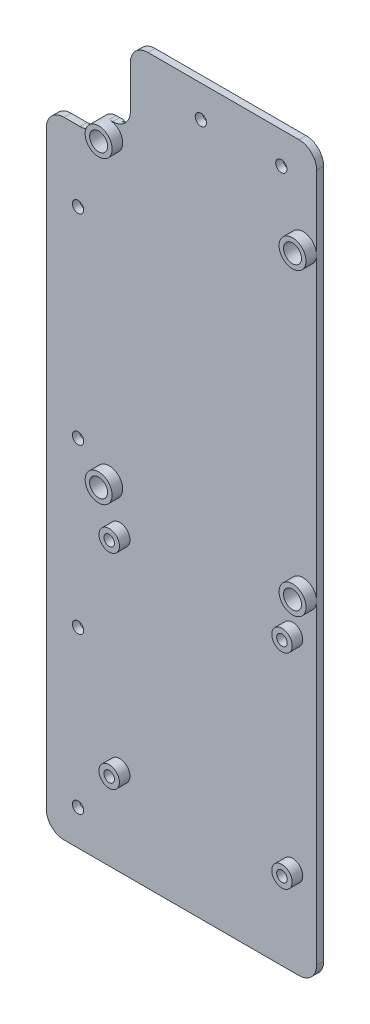
SolidWorks part; units mm, degrees
material "6063-T5"
ref_plane "Front Plane" through (0, 0, 0) normal (1, 0, 0) x (0, 1, 0)
ref_plane "Top Plane" through (0, 0, 0) normal (0, 0, 1) x (0, 1, 0)
ref_plane "Right Plane" through (0, 0, 0) normal (0, 1, 0) x (-1, 0, 0)
sketch "Sketch1" plane through (0, 0, 0) normal (0, 0, 1) x (0, 1, 0)
  line L1 (-42.5, -27.5) -> (42.5, -27.5) construction
  line L2 (-42.5, -27.5) -> (-42.5, 27.5) construction
  line L3 (-42.5, 27.5) -> (42.5, 27.5) construction
  line L4 (42.5, -27.5) -> (42.5, 27.5) construction
  line L5 (-42.5, -27.5) -> (42.5, 27.5) construction
  line L6 (-42.5, 27.5) -> (42.5, -27.5) construction
  circle A0 centre (-42.5, 27.5) radius 2.525
  circle A1 centre (42.5, 27.5) radius 2.525
  circle A2 centre (42.5, -27.5) radius 2.525
  circle A3 centre (-42.5, -27.5) radius 2.525
  circle A4 centre (42.5, 27.5) radius 3.825
  circle A5 centre (-42.5, 27.5) radius 3.825
  circle A6 centre (-42.5, -27.5) radius 3.825
  circle A7 centre (42.5, -27.5) radius 3.825
  point P0 (0, 0)
  dimension "D1" = 1.3
  dimension "D2" = 5.05
  dimension "D3" = 85
  dimension "D4" = 55
extrude "Boss-Extrude1" add sketch "Sketch1" along normal blind 3
sketch "Sketch3" plane through (0, 0, 0) normal (0, 0, -1) x (1, 0, 0)
  line L0 (-31.325, -42.5) -> (-31.325, 42.5)
  line L1 (-27.5, 46.325) -> (27.5, 46.325)
  line L2 (31.325, 42.5) -> (31.325, -42.5)
  line L3 (27.5, -46.325) -> (-27.5, -46.325)
  line L4 (27.5, 46.325) -> (27.5, 42.5) construction
  line L5 (27.5, 42.5) -> (31.325, 42.5) construction
  line L6 (-31.325, -42.5) -> (-27.5, -42.5) construction
  line L7 (-27.5, -42.5) -> (-27.5, -46.325) construction
  arc A0 (-31.325, 42.5) -> (-27.5, 46.325) centre (-27.5, 42.5) cw
  circle A1 centre (-27.5, 42.5) radius 3.825 construction
  arc A2 (31.325, 42.5) -> (27.5, 46.325) centre (27.5, 42.5) ccw
  circle A3 centre (27.5, 42.5) radius 3.825 construction
  arc A4 (-31.325, -42.5) -> (-27.5, -46.325) centre (-27.5, -42.5) ccw
  circle A5 centre (-27.5, -42.5) radius 3.825 construction
  arc A6 (27.5, -46.325) -> (31.325, -42.5) centre (27.5, -42.5) ccw
  circle A7 centre (27.5, -42.5) radius 3.825 construction
extrude "Boss-Extrude2" add sketch "Sketch3" along normal blind 2
sketch "Sketch4" plane through (0, 0, 0) normal (0, 0, 1) x (1, 0, 0)
  line L0 (-27.5, -46.325) -> (-45.325, -46.325)
  line L1 (-45.325, -46.325) -> (-45.325, 40.5)
  line L2 (-45.325, 40.5) -> (-31.325, 40.5)
  line L3 (-31.325, -42.5) -> (-31.325, 42.5) construction
  line L4 (-31.325, 40.5) -> (-31.325, -42.5)
  line L5 (-31.325, -42.5) -> (-27.5, -46.325)
  line L6 (31.325, 42.5) -> (31.325, 68.325)
  line L7 (31.325, 68.325) -> (-21.5, 68.325)
  line L8 (-21.5, 68.325) -> (-21.5, 46.325)
  line L9 (-27.5, 46.325) -> (27.5, 46.325) construction
  line L10 (-21.5, 46.325) -> (27.5, 46.325)
  line L11 (27.5, 46.325) -> (31.325, 42.5)
  line L12 (-36.325, -46.325) -> (-36.325, 40.5) construction
  line L13 (-21.5, 59.325) -> (31.325, 59.325) construction
  line L14 (-36.325, 40.5) -> (-36.325, 59.325) construction
  line L15 (-36.325, 59.325) -> (-21.5, 59.325) construction
  circle A0 centre (-27.5, 42.5) radius 2.525 construction
  circle A1 centre (-27.5, 42.5) radius 2.525 construction
  circle A2 centre (21.325, 59.325) radius 1.6
  circle A3 centre (-1.5, 59.325) radius 1.6
  circle A4 centre (-36.325, 20.5) radius 1.6
  circle A5 centre (-36.325, -36.325) radius 1.6
  dimension "D3" = 6
  dimension "D5" = 3.2
  dimension "D2" = 9
  dimension "D4" = 2
  dimension "D6" = 9
  dimension "D7" = 5
  dimension "D8" = 86.825
  dimension "D9" = 20
  dimension "D10" = 10
  dimension "D11" = 20
  dimension "D12" = 10
  dimension "D13" = 13
extrude "Boss-Extrude3" add sketch "Sketch4" against normal up to surface (2 mm away) up to face at (0, 0, -2)
sketch "Sketch6" plane through (0, 0, 3) normal (0, 0, 1) x (1, 0, 0)
  circle A0 centre (-27.5, 42.5) radius 2.55
  circle A1 centre (27.5, 42.5) radius 2.55
  circle A2 centre (27.5, -42.5) radius 2.55
  circle A3 centre (-27.5, -42.5) radius 2.55
extrude "Cut-Extrude1" cut sketch "Sketch6" against normal offset from surface (4.2 mm away) 4.2 up to face at (-23.675, -42.5, 3)
sketch "Sketch9" plane through (0, 0, 0) normal (0, 0, 1) x (1, 0, 0)
  line L1 (-45.325, -46.325) -> (27.5, -46.325)
  line L2 (-45.325, -46.325) -> (-45.325, -137)
  line L3 (-45.325, -137) -> (31.325, -137)
  line L4 (31.325, -42.5) -> (31.325, -137)
  line L5 (31.325, 42.5) -> (31.325, -42.5) construction
  line L6 (0, 0) -> (0, -83) construction
  line L7 (24.5, -112) -> (-24.5, -112) construction
  line L8 (24.5, -112) -> (24.5, -54) construction
  line L9 (24.5, -54) -> (-24.5, -54) construction
  line L10 (-24.5, -112) -> (-24.5, -54) construction
  line L11 (24.5, -112) -> (-24.5, -54) construction
  line L12 (24.5, -54) -> (-24.5, -112) construction
  arc A0 (27.5, -46.325) -> (31.325, -42.5) centre (27.5, -42.5) ccw
  circle A1 centre (27.5, -42.5) radius 3.825 construction
  circle A2 centre (-24.5, -112) radius 1.5 construction
  circle A3 centre (-24.5, -54) radius 1.5 construction
  circle A4 centre (24.5, -54) radius 1.5 construction
  circle A5 centre (24.5, -112) radius 1.5 construction
  circle A6 centre (27.5, -42.5) radius 2.55 construction
  point P15 (0, -83)
  dimension "D1" = 58
  dimension "D3" = 3
  dimension "D2" = 49
  dimension "D4" = 83
  dimension "D5" = 83
  dimension "D6" = 54
extrude "Boss-Extrude4" add sketch "Sketch9" against normal up to surface (2 mm away) up to face at (-13.365, 21.765, -2)
sketch "Sketch10" plane through (0, 0, 0) normal (0, 0, 1) x (1, 0, 0)
  circle A0 centre (-24.5, -112) radius 1.5
  circle A1 centre (-24.5, -54) radius 1.5
  circle A2 centre (24.5, -54) radius 1.5
  circle A3 centre (24.5, -112) radius 1.5
  circle A5 centre (-24.5, -112) radius 2.9
  circle A6 centre (-24.5, -54) radius 2.9
  circle A7 centre (24.5, -54) radius 2.9
  circle A8 centre (24.5, -112) radius 2.9
  dimension "D1" = 3
  dimension "D2" = 1.4
extrude "Boss-Extrude5" add sketch "Sketch10" along normal blind 3
sketch "Sketch11" plane through (0, 0, 3) normal (0, 0, 1) x (1, 0, 0)
  circle A0 centre (-24.5, -112) radius 1.5
  circle A1 centre (24.5, -112) radius 1.5
  circle A2 centre (24.5, -54) radius 1.5
  circle A3 centre (-24.5, -54) radius 1.5
  circle A4 centre (-24.5, -54) radius 1.5 construction
extrude "Cut-Extrude2" cut sketch "Sketch11" against normal offset from surface (3.1 mm away) 3.1 up to face at (-21.6, -112, 3)
sketch "Sketch5" plane through (0, 0, 0) normal (0, 0, 1) x (1, 0, 0)
  line L0 (-36.325, -36.325) -> (-36.325, 59.325) construction
  line L1 (-36.325, 59.325) -> (21.325, 59.325) construction
ref_axis "Axis1" through (-36.325, 59.325, 0) along (1, 0, 0)
ref_axis "Axis2" through (-36.325, -36.325, 0) along (0, 1, 0)
fillet "Fillet1" radius 5 7 edges at (-45.325, 40.5, -1) (-21.5, 68.325, -1) (31.325, 68.325, -1) (-21.5, 46.325, -1) (-31.325, 40.5, -1) (-45.325, -137, -1) (31.325, -137, -1)
sketch "Sketch12" plane through (0, 0, 0) normal (0, 0, 1) x (1, 0, 0)
  line L0 (-36.325, -36.325) -> (-36.325, -137) construction
  line L1 (-40.325, -137) -> (26.325, -137) construction
  circle A0 centre (-36.325, -127) radius 1.6
  circle A1 centre (-36.325, -36.325) radius 1.6 construction
  circle A2 centre (-36.325, -82.7952) radius 1.6
  dimension "D1" = 10
extrude "Cut-Extrude3" cut sketch "Sketch12" against normal up to surface (2 mm away) up to face at (-15.7516, 1.96, -2)
sketch "Sketch14" plane through (0, 0, -2) normal (0, 0, -1) x (0, 1, 0)
  line L0 (19.725, -26.725) -> (49.725, 3.275)
  line L1 (49.725, 3.275) -> (49.725, -24.7412)
  line L4 (-36.325, -36.325) -> (59.325, -36.325) construction
  line L5 (49.725, -24.7412) -> (59.325, -24.7412) construction
  line L6 (59.325, -36.325) -> (59.325, 21.325) construction
  line L7 (45.1494, -24.7412) -> (49.725, -24.7412)
  line L8 (38.7543, -26.725) -> (19.725, -26.725)
  line L9 (29.2397, -26.725) -> (29.2397, -36.325) construction
  circle A1 centre (42.5, -27.5) radius 3.825 construction
  circle A2 centre (42.5, -27.5) radius 3.825 construction
  arc A3 (38.7543, -26.725) -> (45.1494, -24.7412) centre (42.5, -27.5) cw
  dimension "D4" = 9.6
  dimension "D1" = 30
  dimension "D2" = 30
extrude "Cut-Extrude4" cut sketch "Sketch14" against normal blind 1
fillet "Fillet2" radius 1 5 edges at (-24.7412, 45.897, -2) (-23.8467, 41.3667, -2) (-26.725, 29.2397, -2) (-9.244, 49.725, -2) (-11.725, 34.725, -2)
